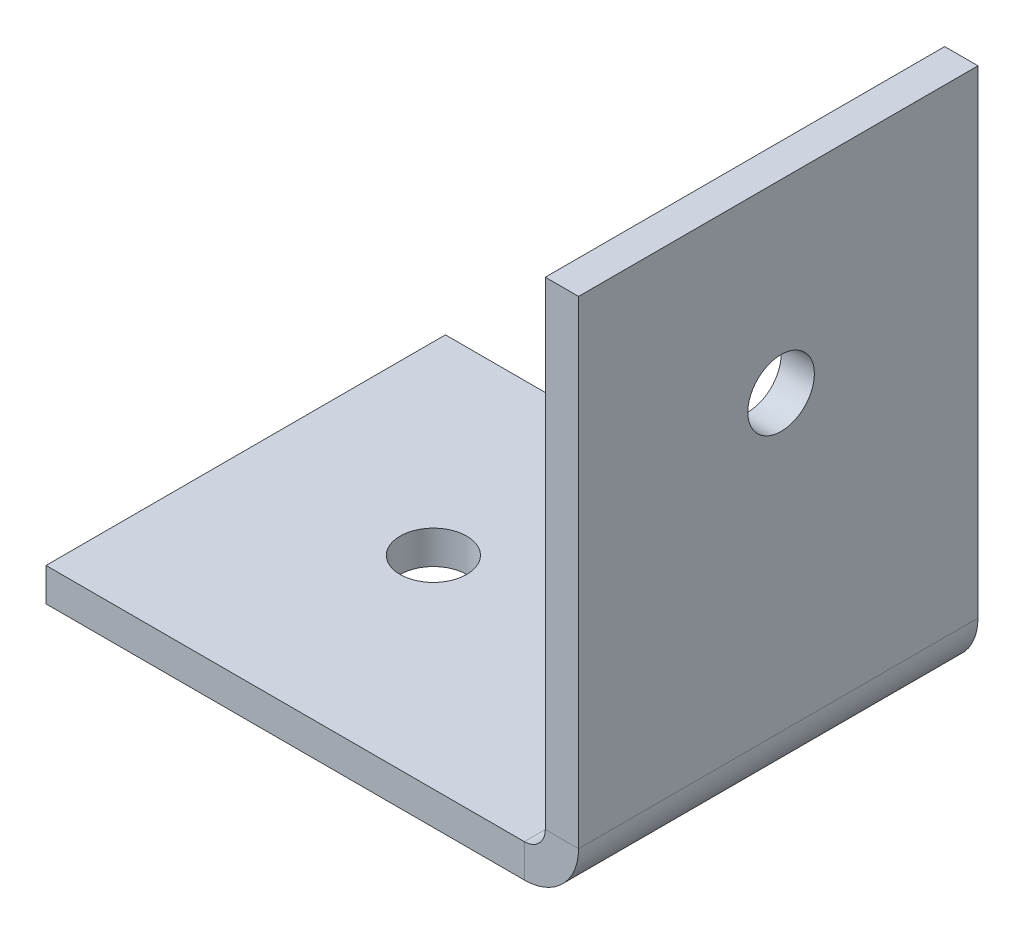
SolidWorks part; units mm, degrees
note: The reader was unsure of these and kept them because the rebuilt part matched: flange length of "Edge-Flange1".
ref_plane "Front Plane" through (0, 0, 0) normal (0, 0, 1) x (1, 0, 0)
ref_plane "Top Plane" through (0, 0, 0) normal (0, 1, 0) x (1, 0, 0)
ref_plane "Right Plane" through (0, 0, 0) normal (1, 0, 0) x (0, 0, -1)
sketch "Sketch1" plane through (0, 0, 0) normal (0, 1, 0) x (1, 0, 0)
  line L1 (0, 0) -> (25.4, 0)
  line L2 (0, 0) -> (0, 19.05)
  line L3 (0, 19.05) -> (25.4, 19.05)
  line L4 (25.4, 0) -> (25.4, 19.05)
  dimension "D1" = 25.4
  dimension "D2" = 19.05
base flange "Base-Flange1" sketch "Sketch1" thickness 1.5875 reverse thickness direction no parameters "D1"=1
edge flange "Edge-Flange1" sketch "Sketch8" flange angle 90 flange length 25.4 flange position material inside bend radius 1 thickness 1.5875 relief rectangular parameters "D6"=10
sketch "Sketch8" plane through (25.4, 0, 0) normal (1, 0, 0) x (0, 0, -1)
  line L0 (0, 0) -> (19.05, 0) construction
  line L1 (0, 0) -> (19.05, 0)
  line L2 (0, 0) -> (0, 23.8125)
  line L3 (0, 23.8125) -> (19.05, 23.8125)
  line L4 (19.05, 23.8125) -> (19.05, 0)
bend "EdgeBend1" bend radius 1 bend angle 90 parameters "D5"=1
hole_wizard "1/8 (0.125) Diameter Hole1" positions "Sketch9" profile "Sketch10" hole size "1/8" standard "ANSI Inch" end condition through all
sketch "Sketch9" plane through (25.4, 0, 0) normal (1, 0, 0) x (0, 0, -1)
  point P0 (9.6582, 14.9946)
sketch "Sketch10" plane through (25.4, 14.9946, -9.6582) normal (0, 1, 0) x (0, 0, -1)
  line L0 (0, 0) -> (0, 25.4)
  line L1 (0, 25.4) -> (1.5875, 25.4)
  line L2 (1.5875, 25.4) -> (1.5875, 0)
  line L5 (1.5875, 0) -> (0, 0)
  line L11 (0, -6.35) -> (0, 107.95) construction
  dimension "Thru Hole Dia." = 3.175
  dimension "Thru Hole Depth" = 25.4
hole_wizard "1/8 (0.125) Diameter Hole2" positions "Sketch11" profile "Sketch12" hole size "1/8" standard "ANSI Inch" end condition through all
sketch "Sketch11" plane through (0, -1.5875, 0) normal (0, -1, 0) x (-1, 0, 0)
  point P4 (-8.8179, 9.6582)
sketch "Sketch12" plane through (8.8179, -1.5875, -9.6582) normal (1, 0, 0) x (0, 0, -1)
  line L0 (0, 0) -> (0, 25.4)
  line L1 (0, 25.4) -> (1.5875, 25.4)
  line L2 (1.5875, 25.4) -> (1.5875, 0)
  line L5 (1.5875, 0) -> (0, 0)
  line L11 (0, -6.35) -> (0, 107.95) construction
  dimension "Thru Hole Dia." = 3.175
  dimension "Thru Hole Depth" = 25.4
sketch "Bend-Lines1" [suppressed] plane through (0, 0, 0) normal (0, 1, 0) x (1, 0, 0)
sketch "Bounding-Box1" [suppressed] plane through (0, 0, 0) normal (0, 1, 0) x (1, 0, 0)
sheet metal parameters "Sheet-Metal1" thickness 1.5875 parameters "D1"=1
flat pattern "Flat-Pattern1" [suppressed]
sketch "Bend-Lines2" plane through (0, 0, 0) normal (0, 1, 0) x (1, 0, 0)
sketch3d "Bounding-Box2" [suppressed]
  line L0 (-25.4, 19.05, 0) -> (0, 19.05, 0) construction
  line L1 (-25.4, 0, 0) -> (0, 0, 0) construction
  line L2 (-25.4, 19.05, 0) -> (-25.4, 0, 0) construction
  line L3 (0, 19.05, 0) -> (0, 0, 0) construction
sheet metal parameters "Sheet-Metal2" thickness 1.5875 parameters "D1"=1
flat pattern "Flat-Pattern1"
sketch "Bend-Lines2" plane through (0, 0, 0) normal (0, 1, 0) x (1, 0, 0)
  line L0 (24.2213, 0) -> (24.2213, 19.05) construction
  line L1 (24.2213, 0) -> (24.2213, 19.05) construction
sketch3d "Bounding-Box2" [suppressed]
  line L0 (48.4426, 19.05, 0) -> (0, 19.05, 0) construction
  line L1 (48.4426, 0, 0) -> (0, 0, 0) construction
  line L2 (48.4426, 19.05, 0) -> (48.4426, 0, 0) construction
  line L3 (0, 19.05, 0) -> (0, 0, 0) construction
bend of the flat pattern "Flatten-<EdgeBend1>1"
sheet metal parameters "Sheet-Metal3" thickness 1.5875 parameters "D1"=1
flat pattern "Flat-Pattern1"
sketch "Bend-Lines2" plane through (0, 0, 0) normal (0, 1, 0) x (1, 0, 0)
  line L0 (24.2213, 0) -> (24.2213, 19.05) construction
  line L1 (24.2213, 0) -> (24.2213, 19.05) construction
sketch3d "Bounding-Box2" [suppressed]
  line L0 (48.4426, 19.05, 0) -> (0, 19.05, 0) construction
  line L1 (48.4426, 0, 0) -> (0, 0, 0) construction
  line L2 (48.4426, 19.05, 0) -> (48.4426, 0, 0) construction
  line L3 (0, 19.05, 0) -> (0, 0, 0) construction
bend of the flat pattern "Flatten-<EdgeBend1>1"
sheet metal parameters "Sheet-Metal4" thickness 1.5875 parameters "D1"=1
flat pattern "Flat-Pattern1"
sketch "Bend-Lines2" plane through (0, 0, 0) normal (0, 1, 0) x (1, 0, 0)
  line L0 (24.2213, 0) -> (24.2213, 19.05) construction
  line L1 (24.2213, 0) -> (24.2213, 19.05) construction
sketch3d "Bounding-Box2" [suppressed]
  line L0 (48.4426, 19.05, 0) -> (0, 19.05, 0) construction
  line L1 (48.4426, 0, 0) -> (0, 0, 0) construction
  line L2 (48.4426, 19.05, 0) -> (48.4426, 0, 0) construction
  line L3 (0, 19.05, 0) -> (0, 0, 0) construction
bend of the flat pattern "Flatten-<EdgeBend1>1"
